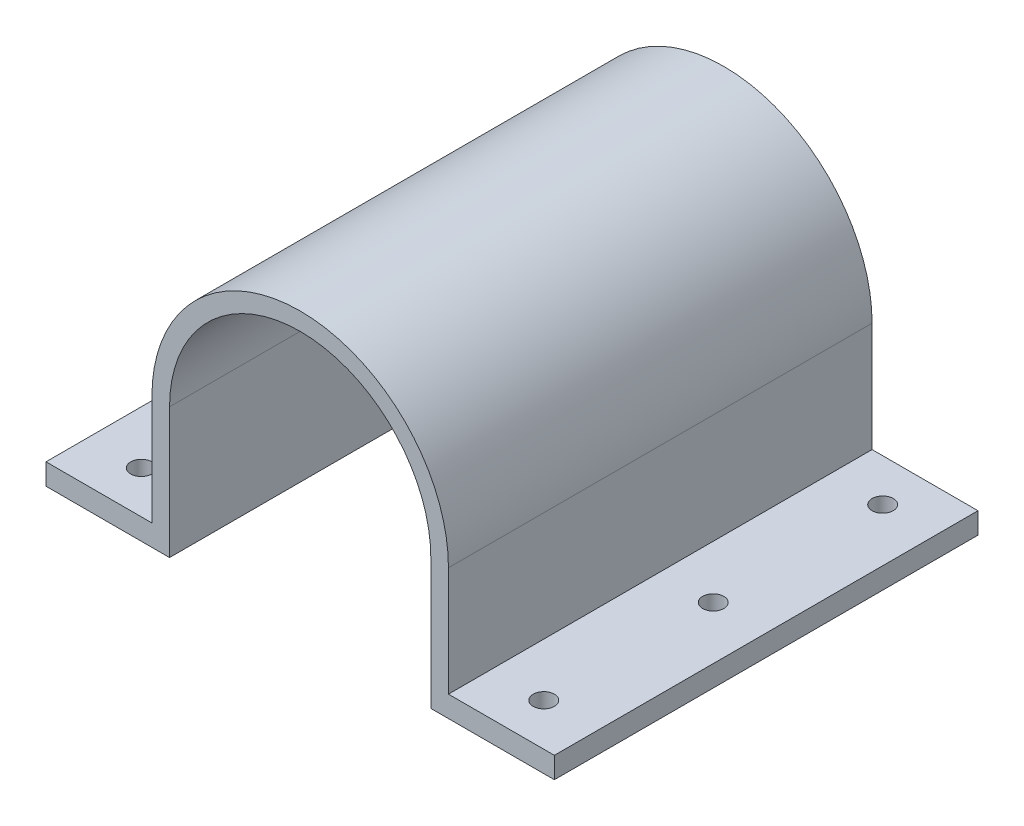
SolidWorks part; units mm, degrees
ref_plane "Front Plane" through (0, 0, 0) normal (0, 0, 1) x (1, 0, 0)
ref_plane "Top Plane" through (0, 0, 0) normal (0, 1, 0) x (1, 0, 0)
ref_plane "Right Plane" through (0, 0, 0) normal (1, 0, 0) x (0, 0, -1)
sketch "Sketch1" plane through (0, 0, 0) normal (0, 0, 1) x (1, 0, 0)
  line L0 (-21, 0) -> (-21, -15.5)
  line L1 (-21, -15.5) -> (-36, -15.5)
  line L2 (-36, -15.5) -> (-36, -18.5)
  line L3 (-36, -18.5) -> (36, -18.5)
  line L4 (36, -18.5) -> (36, -15.5)
  line L5 (36, -15.5) -> (21, -15.5)
  line L6 (21, -15.5) -> (21, 0)
  line L7 (0, 0) -> (0, 7) construction
  line L8 (0, 0) -> (-15.5, 0) construction
  line L9 (-21, -15.5) -> (21, -15.5) construction
  arc A0 (21, 0) -> (-21, 0) centre (0, 0) ccw
  circle A2 centre (-15.5, 0) radius 1.65
  circle A3 centre (-7.75, 13.4234) radius 1.65
  circle A4 centre (7.75, 13.4234) radius 1.65
  circle A5 centre (15.5, 0) radius 1.65
  circle A6 centre (7.75, -13.4234) radius 1.65
  circle A7 centre (-7.75, -13.4234) radius 1.65
  circle A8 centre (0, 0) radius 18.5 construction
  circle A9 centre (0, 7) radius 6.15
  point P15 (0, -18.5)
  point P27 (0, 0)
  dimension "D1" = 42
  dimension "D6" = 0
  dimension "D7" = 3.3
  dimension "D10" = 37
  dimension "D11" = 2.5
  dimension "D3" = 12.3
  dimension "D2" = 7
  dimension "D4" = 72
  dimension "D5" = 3
  dimension "D8" = 15.5
  dimension "D9" = 6
extrude "Boss-Extrude1" add sketch "Sketch1" along normal blind 60
sketch "Sketch2" plane through (0, 0, 60) normal (0, 0, 1) x (1, 0, 0)
  line L0 (-18.5, 0) -> (-18.5, -18.5)
  line L1 (-36, -18.5) -> (36, -18.5) construction
  line L2 (-18.5, -18.5) -> (18.5, -18.5)
  line L3 (18.5, -18.5) -> (18.5, 0)
  arc A0 (18.5, 0) -> (-18.5, 0) centre (0, 0) ccw
  arc A1 (-18.5, 0) -> (18.5, 0) centre (0, 0) ccw construction
  point P7 (0, 0)
  dimension "D1" = 37
extrude "Cut-Extrude1" cut sketch "Sketch2" against normal blind 57
sketch "Sketch3" plane through (0, -15.5, 0) normal (0, 1, 0) x (1, 0, 0)
  line L0 (0, 0) -> (0, -60) construction
  line L1 (-21, -60) -> (21, -60) construction
  line L2 (-28.5, 0) -> (-28.5, -60) construction
  line L3 (-21, 0) -> (-36, 0) construction
  line L4 (-21, -60) -> (-36, -60) construction
  circle A0 centre (-28.5, -30) radius 1.5
  circle A1 centre (-28.5, -6) radius 1.5
  circle A2 centre (-28.5, -54) radius 1.5
  circle A3 centre (28.5, -54) radius 1.5
  circle A4 centre (28.5, -6) radius 1.5
  circle A5 centre (28.5, -30) radius 1.5
  dimension "D1" = 24
  dimension "D2" = 24
  dimension "D3" = 3
extrude "Cut-Extrude2" cut sketch "Sketch3" against normal through all
